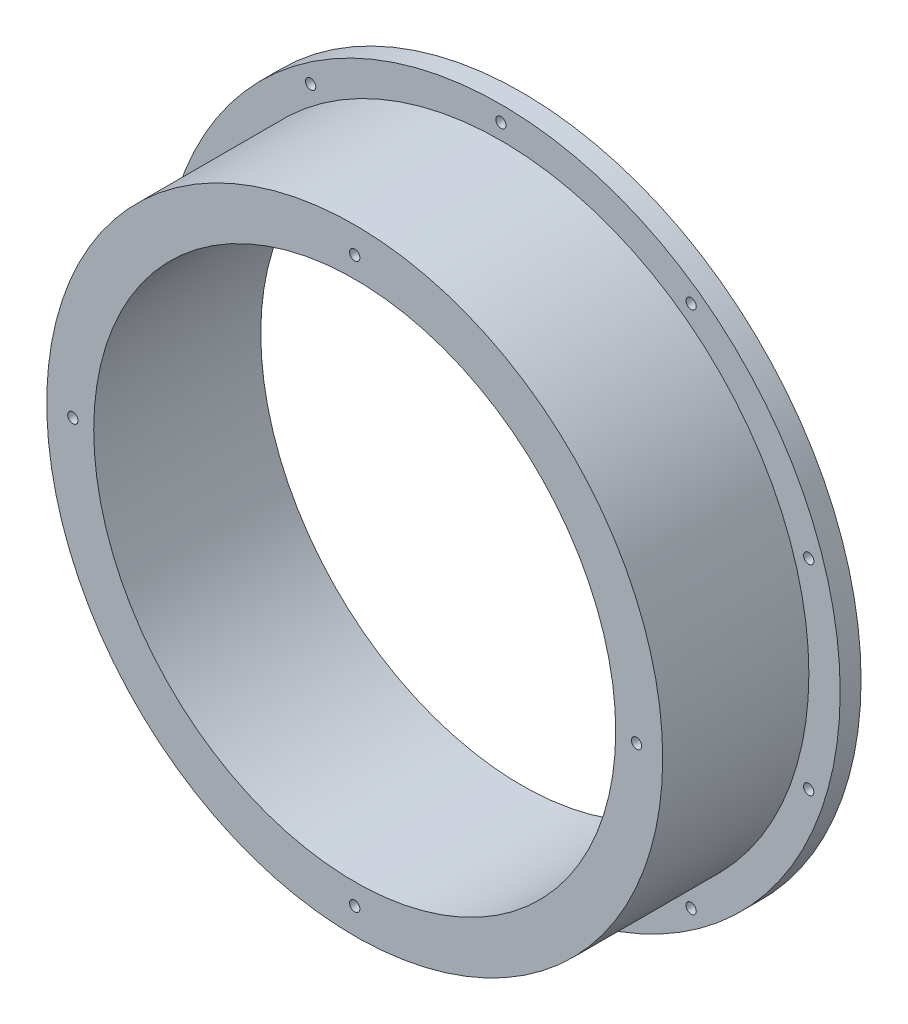
SolidWorks part; units mm, degrees
material "6061 Alloy"
ref_plane "Front Plane" through (0, 0, 0) normal (0, 0, 1) x (1, 0, 0)
ref_plane "Top Plane" through (0, 0, 0) normal (0, 1, 0) x (1, 0, 0)
ref_plane "Right Plane" through (0, 0, 0) normal (1, 0, 0) x (0, 0, -1)
sketch "Sketch1" plane through (0, 0, 0) normal (0, 1, 0) x (1, 0, 0)
  line L0 (63.5, 20.32) -> (82.55, 20.32)
  line L1 (82.55, 20.32) -> (82.55, 15.24)
  line L2 (82.55, 15.24) -> (74.93, 15.24)
  line L3 (74.93, 15.24) -> (74.93, -20.32)
  line L4 (74.93, -20.32) -> (63.5, -20.32)
  line L7 (63.5, 20.32) -> (63.5, -20.32)
  line L8 (0, 0) -> (63.5, 0) construction
  line L9 (0, 0) -> (0, 46.6158) construction
  point P10 (63.5, 0)
  dimension "D1" = 35.56
  dimension "D2" = 74.93
  dimension "D3" = 82.55
  dimension "D4" = 5.08
  dimension "D5" = 63.5
revolve "Base Boss" add sketch "Sketch1" angle 360 about L9
sketch "Sketch2" plane through (0, 0, 20.32) normal (0, 0, 1) x (1, 0, 0)
  line L0 (0, 68.58) -> (0, 0) construction
  line L1 (0, 0) -> (68.58, 0) construction
  circle A0 centre (0, 0) radius 68.58 construction
  circle A1 centre (0, 68.58) radius 1.25
  circle A2 centre (68.58, 0) radius 1.25
  circle A3 centre (0, -68.58) radius 1.25
  circle A4 centre (-68.58, 0) radius 1.25
  dimension "D1" = 137.16
  dimension "D2" = 2.5
  dimension "D3" = 4
extrude "Internal Mounting Holes" cut sketch "Sketch2" against normal blind 4
sketch "Sketch3" plane through (0, 0, -20.32) normal (0, 0, -1) x (-1, 0, 0)
  circle A0 centre (0, 0) radius 78.74 construction
  circle A1 centre (0, 78.74) radius 1.25
  circle A2 centre (46.2822, 63.702) radius 1.25
  circle A3 centre (74.8862, 24.332) radius 1.25
  circle A4 centre (74.8862, -24.332) radius 1.25
  circle A5 centre (46.2822, -63.702) radius 1.25
  circle A6 centre (0, -78.74) radius 1.25
  circle A7 centre (-46.2822, -63.702) radius 1.25
  circle A8 centre (-74.8862, -24.332) radius 1.25
  circle A9 centre (-74.8862, 24.332) radius 1.25
  circle A10 centre (-46.2822, 63.702) radius 1.25
  dimension "D1" = 157.48
  dimension "D2" = 2.5
  dimension "D3" = 10
extrude "Endcap Mounting Holes" cut sketch "Sketch3" against normal through all both and the other way through all
ref_axis "Axis" through (0, 0, -20.32) along (0, 0, 1)
